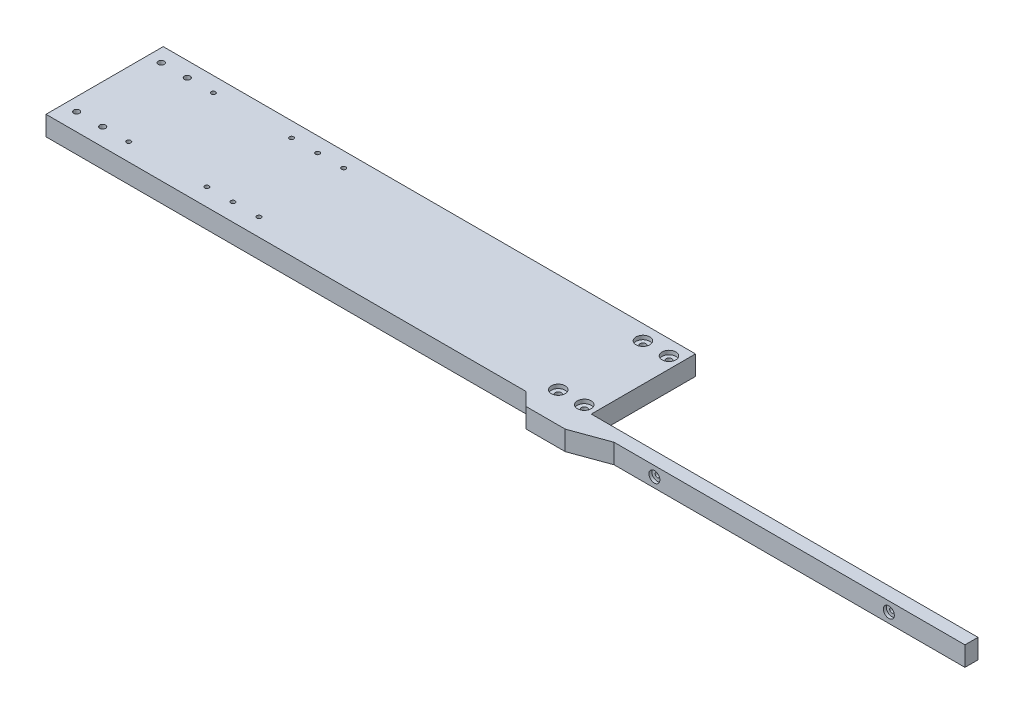
SolidWorks part; units mm, degrees
material "201 Annealed Stainless Steel (SS)"
ref_plane "Front Plane" through (0, 0, 0) normal (0, 0, 1) x (1, 0, 0)
ref_plane "Top Plane" through (0, 0, 0) normal (0, 1, 0) x (1, 0, 0)
ref_plane "Right Plane" through (0, 0, 0) normal (1, 0, 0) x (0, 0, -1)
sketch "Sketch1" plane through (0, 0, 0) normal (0, 0, 1) x (1, 0, 0)
  line L1 (148.44, -7.5) -> (-148.44, -7.5)
  line L2 (148.44, -7.5) -> (148.44, 7.5)
  line L3 (148.44, 7.5) -> (-148.44, 7.5)
  line L4 (-148.44, -7.5) -> (-148.44, 7.5)
  line L5 (148.44, -7.5) -> (-148.44, 7.5) construction
  line L6 (148.44, 7.5) -> (-148.44, -7.5) construction
  point P0 (0, 0)
  dimension "D1" = 296.88
  dimension "D2" = 15
extrude "Boss-Extrude1" add sketch "Sketch1" against normal blind 10 contours L3 L4 L1 L2
sketch "To_rack_Holes" plane through (0, 0, 0) normal (0, 0, 1) x (1, 0, 0)
  point P0 (-90, 0)
  point P1 (90, 0)
  dimension "D1" = 180
  dimension "D2" = 90
hole_wizard "CBORE for M3 Hex Head Machine Screw1" positions "Sketch3" profile "Sketch4" counterbore size "M3" standard "ANSI Metric" end condition through all
sketch "Sketch3" plane through (0, 0, 0) normal (0, 0, 1) x (1, 0, 0)
  point P0 (-90, 0)
  point P3 (90, 0)
sketch "Sketch4" plane through (-90, 0, 0) normal (1, 0, 0) x (0, -1, 0)
  line L0 (0, 0) -> (0, 10)
  line L1 (0, 10) -> (1.7, 10)
  line L3 (1.7, 10) -> (1.7, 2.3)
  line L4 (1.7, 2.3) -> (4.2, 2.3)
  line L5 (4.2, 2.3) -> (4.2, 0)
  line L7 (4.2, 0) -> (0, 0)
  line L11 (0, -6.35) -> (0, 107.95) construction
  dimension "Thru Hole Dia." = 3.4
  dimension "Thru Hole Depth" = 10
  dimension "C'Bore Dia." = 8.4
  dimension "C'Bore Depth" = 2.3
sketch "Sketch5" plane through (0, 7.5, 0) normal (0, 1, 0) x (1, 0, 0)
  line L0 (-148.44, 0) -> (-188.44, 0)
  line L1 (-188.44, 0) -> (-188.44, 90)
  line L2 (-188.44, 90) -> (-148.44, 90)
  line L3 (-148.44, 90) -> (-148.44, 0)
  dimension "D1" = 90
  dimension "D2" = 40
extrude "Boss-Extrude2" add sketch "Sketch5" against normal up to surface (15 mm away) up to face at (0, -7.5, -5)
sketch "Sketch8" plane through (0, 7.5, 0) normal (0, 1, 0) x (1, 0, 0)
  point P0 (-177.3113, 78.5)
  point P1 (-157.3113, 78.5)
  point P2 (-177.3113, 13.5)
  point P7 (-157.3113, 13.5)
hole_wizard "CBORE for M4 Hex Head Machine Screw1" positions "Sketch11" profile "Sketch10" counterbore size "M4" standard "ANSI Metric" end condition through all
sketch "Sketch11" plane through (0, 7.5, 0) normal (0, 1, 0) x (1, 0, 0)
  point P0 (-177.3113, 13.5)
  point P3 (-157.3113, 13.5)
  point P7 (-177.3113, 78.5)
  point P10 (-157.3113, 78.5)
sketch "Sketch10" plane through (-177.3113, 7.5, -13.5) normal (1, 0, 0) x (0, 0, 1)
  line L0 (0, 0) -> (0, 15)
  line L1 (0, 15) -> (2.25, 15)
  line L3 (2.25, 15) -> (2.25, 3)
  line L4 (2.25, 3) -> (5.295, 3)
  line L5 (5.295, 3) -> (5.295, 0)
  line L7 (5.295, 0) -> (0, 0)
  line L11 (0, -6.35) -> (0, 107.95) construction
  dimension "Thru Hole Dia." = 4.5
  dimension "Thru Hole Depth" = 15
  dimension "C'Bore Dia." = 10.59
  dimension "C'Bore Depth" = 3
sketch "Sketch12" plane through (0, 7.5, 0) normal (0, 1, 0) x (1, 0, 0)
  line L0 (-188.44, 0) -> (-178.44, -10)
  line L1 (-178.44, -10) -> (-148.44, -10)
  line L2 (-148.44, -10) -> (-120.9652, 0)
  line L3 (148.44, 0) -> (-188.44, 0) construction
  line L4 (-188.44, 0) -> (-120.9652, 0)
  dimension "D1" = 45
  dimension "D2" = 10
  dimension "D3" = 160
extrude "Boss-Extrude3" add sketch "Sketch12" against normal up to surface (15 mm away) up to face at (-177.3113, -7.5, -11.25)
sketch "Sketch13" plane through (0, 7.5, 0) normal (0, 1, 0) x (1, 0, 0)
  line L0 (-188.44, 90) -> (-557.0759, 90)
  line L1 (-557.0759, 90) -> (-557.0759, 0)
  line L2 (-557.0759, 0) -> (-188.44, 0)
  line L3 (-557.0759, 37.3) -> (-557.0759, 54.7) construction
  line L4 (-188.44, 90) -> (-188.44, 0)
  point P8 (-547.0759, 78.5)
  point P9 (-527.0759, 78.5)
  point P11 (-527.0759, 13.5)
  point P13 (-547.0759, 13.5)
extrude "Boss-Extrude4" add sketch "Sketch13" against normal up to surface (15 mm away) up to face at (-177.3113, -7.5, -11.25)
hole_wizard "M4 Clearance Hole1" positions "Sketch14" profile "Sketch15" hole size "M4" standard "ANSI Metric" end condition through all
sketch "Sketch14" plane through (0, 7.5, 0) normal (0, 1, 0) x (1, 0, 0)
  point P0 (-547.0759, 78.5)
  point P3 (-527.0759, 78.5)
  point P6 (-527.0759, 13.5)
  point P9 (-547.0759, 13.5)
sketch "Sketch15" plane through (-547.0759, 7.5, -78.5) normal (1, 0, 0) x (0, 0, 1)
  line L0 (0, 0) -> (0, 15)
  line L1 (0, 15) -> (2.25, 15)
  line L2 (2.25, 15) -> (2.25, 0)
  line L5 (2.25, 0) -> (0, 0)
  line L11 (0, -6.35) -> (0, 107.95) construction
  dimension "Thru Hole Dia." = 4.5
  dimension "Thru Hole Depth" = 15
sketch "Sketch16" plane through (0, 7.5, 0) normal (0, 1, 0) x (1, 0, 0)
  point P0 (-507.0759, 78.5)
  point P1 (-447.0759, 78.5)
  point P3 (-427.0759, 78.5)
  point P5 (-407.0759, 78.5)
  point P7 (-507.0759, 13.5)
  point P9 (-447.0759, 13.5)
  point P11 (-427.0759, 13.5)
  point P13 (-407.0759, 13.5)
hole_wizard "M4x0.7 Tapped Hole1" positions "Sketch17" profile "Sketch18" tap size "M4x0.7" standard "ANSI Metric"
sketch "Sketch17" plane through (0, 7.5, 0) normal (0, 1, 0) x (1, 0, 0)
  point P0 (-507.0759, 78.5)
  point P3 (-507.0759, 13.5)
  point P6 (-447.0759, 13.5)
  point P9 (-427.0759, 13.5)
  point P12 (-407.0759, 13.5)
  point P15 (-407.0759, 78.5)
  point P18 (-427.0759, 78.5)
  point P21 (-447.0759, 78.5)
sketch "Sketch18" plane through (-507.0759, 7.5, -78.5) normal (1, 0, 0) x (0, 0, 1)
  line L0 (0, 0) -> (0, 11.0914)
  line L1 (0, 11.0914) -> (1.65, 10.1)
  line L2 (1.65, 10.1) -> (1.65, 0)
  line L5 (1.65, 0) -> (0, 0)
  line L10 (0, 11.0914) -> (-1.65, 10.1) construction
  line L11 (0, -6.35) -> (0, 107.95) construction
  dimension "Tap Drill Dia." = 3.3
  dimension "Tap Drill Depth" = 10.1
  dimension "Drill Angle" = 118
cosmetic thread "Hole Thread1" parameters "D1"=8, "D2"=4
cosmetic thread "Hole Thread2" parameters "D1"=8, "D2"=4
cosmetic thread "Hole Thread3" parameters "D1"=8, "D2"=4
cosmetic thread "Hole Thread4" parameters "D1"=8, "D2"=4
cosmetic thread "Hole Thread5" parameters "D1"=8, "D2"=4
cosmetic thread "Hole Thread6" parameters "D1"=8, "D2"=4
cosmetic thread "Hole Thread7" parameters "D1"=8, "D2"=4
cosmetic thread "Hole Thread8" parameters "D1"=8, "D2"=4
